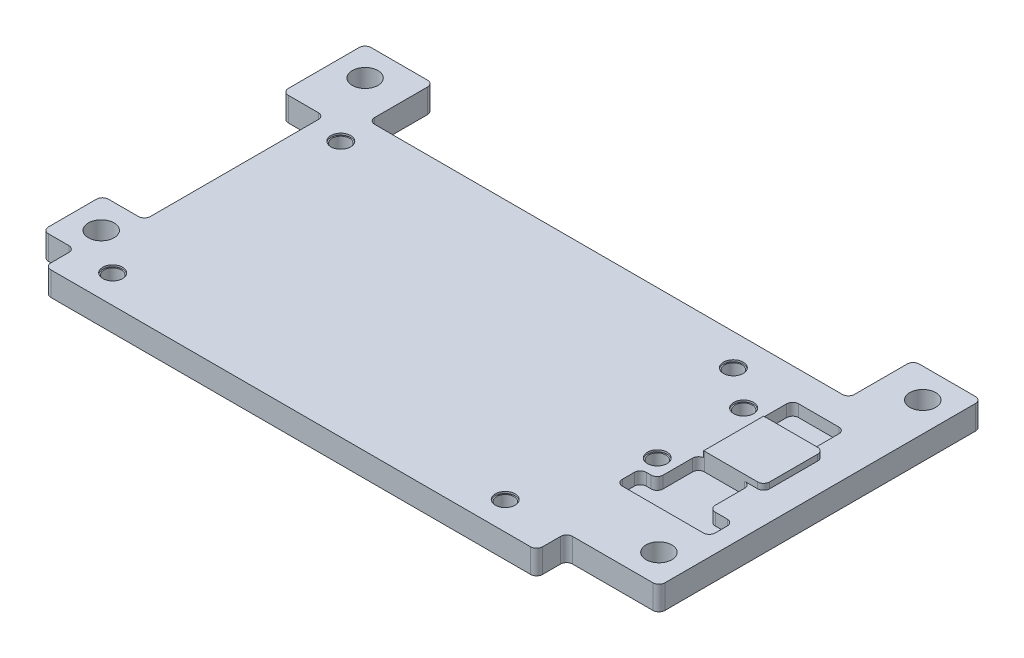
SolidWorks part; units mm, degrees
ref_plane "Front Plane" through (0, 0, 0) normal (0, 0, 1) x (1, 0, 0)
ref_plane "Top Plane" through (0, 0, 0) normal (0, 1, 0) x (1, 0, 0)
ref_plane "Right Plane" through (0, 0, 0) normal (1, 0, 0) x (0, 0, -1)
sketch "Sketch1" plane through (0, 0, 0) normal (0, 1, 0) x (1, 0, 0)
  line L0 (-97.9, 0) -> (-97.9, -53.8) construction
  line L1 (0, 0) -> (-102.8, 0)
  line L2 (0, 0) -> (0, -53.8)
  line L3 (0, -53.8) -> (-15.4, -53.8)
  line L4 (-102.8, 0) -> (-102.8, -53.8)
  line L5 (-102.8, -4.9) -> (0.8959, -4.9) construction
  line L6 (-102.8, -48.9) -> (0, -48.9) construction
  line L7 (-4.9, 0) -> (-4.9, -53.8) construction
  line L8 (-97.4, -53.8) -> (-97.4, -58.8)
  line L9 (-97.4, -58.8) -> (-15.4, -58.8)
  line L10 (-15.4, -58.8) -> (-15.4, -53.8)
  line L13 (-97.4, -53.8) -> (-102.8, -53.8)
  line L14 (-15.4, -53.8) -> (-97.4, -53.8) construction
  circle A0 centre (-97.9, -4.9) radius 2.15
  circle A1 centre (-97.9, -48.9) radius 2.15
  circle A2 centre (-4.9, -4.9) radius 2.15
  circle A3 centre (-4.9, -48.9) radius 2.15
  point P9 (-97.9, -4.9)
  point P14 (-4.9, -4.9)
  point P15 (-97.9, -48.9)
  point P16 (-4.9, -48.9)
  dimension "D7" = 4.3
  dimension "D1" = 102.8
  dimension "D2" = 53.8
  dimension "D3" = 4.9
  dimension "D4" = 4.9
  dimension "D5" = 4.9
  dimension "D6" = 4.9
  dimension "D8" = 82
  dimension "D9" = 5
  dimension "D10" = 5.4
extrude "Main" add sketch "Sketch1" along normal blind 4
sketch "Display Mount Locations" plane through (0, 4, 0) normal (0, 1, 0) x (1, 0, 0)
  line L1 (-90.8, -54.09) -> (-25.34, -54.09) construction
  line L2 (-90.8, -54.09) -> (-90.8, -16.05) construction
  line L3 (-90.8, -16.05) -> (-25.34, -16.05) construction
  line L4 (-25.34, -54.09) -> (-25.34, -16.05) construction
  line L5 (-90.8, -35.07) -> (-102.8, -35.07) construction
  line L7 (-102.8, 0) -> (-102.8, -53.8) construction
  line L9 (-15.4, -53.8) -> (0, -53.8) construction
  point P5 (-90.8, -16.05)
  point P6 (-25.34, -16.05)
  point P7 (-25.34, -54.09)
  point P8 (-90.8, -54.09)
  dimension "D1" = 65.46
  dimension "D2" = 38.04
  dimension "D3" = 0.29
  dimension "D4" = 12
sketch "Sketch4" plane through (0, 4, 0) normal (0, 1, 0) x (1, 0, 0)
  line L0 (-102.8, 0) -> (-102.8, -53.8) construction
  line L1 (-102.8, -13.8) -> (-95.8, -13.8)
  line L2 (-102.8, -13.8) -> (-102.8, -43.8)
  line L3 (-102.8, -43.8) -> (-95.8, -43.8)
  line L4 (-95.8, -13.8) -> (-95.8, -43.8)
  line L5 (-51.4, 0) -> (-51.4, -58.8) construction
  line L6 (0, 0) -> (-102.8, 0) construction
  line L8 (-102.8, -53.8) -> (-97.4, -53.8) construction
  line L13 (-97.4, -58.8) -> (-15.4, -58.8) construction
  dimension "D1" = 7
  dimension "D2" = 30
  dimension "D3" = 10
extrude "Wire Escapes" cut sketch "Sketch4" against normal up to next
sketch "Sketch5" plane through (0, 4, 0) normal (0, 1, 0) x (1, 0, 0)
  line L0 (0, 0) -> (-102.8, 0) construction
  line L1 (-91.4, 0) -> (-11.4, 0)
  line L2 (-91.4, 0) -> (-91.4, -10.8)
  line L3 (-91.4, -10.8) -> (-11.4, -10.8)
  line L4 (-11.4, 0) -> (-11.4, -10.8)
  line L5 (-91.4, -5.4) -> (-102.8, -5.4) construction
  line L7 (-11.4, -5.4) -> (0, -5.4) construction
  line L9 (-95.8, -13.8) -> (-102.8, -13.8) construction
  line L10 (-102.8, 0) -> (-102.8, -13.8) construction
  line L11 (0, -53.8) -> (0, 0) construction
  dimension "D1" = 80
  dimension "D2" = 3
extrude "Button Clearance" cut sketch "Sketch5" against normal up to next
sketch "Encoder Switch Mounting Points" plane through (0, 4, 0) normal (0, 1, 0) x (1, 0, 0)
  line L5 (0, -53.8) -> (0, 0) construction
  line L6 (-1, -15.8) -> (-19.7, -15.8) construction
  line L7 (-1, -15.8) -> (-1, -42.4) construction
  line L8 (-1, -42.4) -> (-19.7, -42.4) construction
  line L9 (-19.7, -15.8) -> (-19.7, -42.4) construction
  line L10 (-91.4, -10.8) -> (-11.4, -10.8) construction
  line L11 (-18.675, -15.8) -> (-18.675, -42.4) construction
  point P8 (-18.675, -35.4)
  point P9 (-18.675, -21)
  dimension "D1" = 1
  dimension "D2" = 18.7
  dimension "D3" = 26.6
  dimension "D4" = 5
  dimension "D5" = 2.05
  dimension "D6" = 5.2
  dimension "D7" = 7
hole_wizard "M2 Heat Sets" positions "3DSketch1" profile "Sketch3" counterbore size "M72" standard "ANSI Metric"
sketch3d "3DSketch1"
  point P0 (-90.8, 4, 16.05)
  point P3 (-90.8, 4, 54.09)
  point P6 (-25.34, 4, 54.09)
  point P9 (-25.34, 4, 16.05)
  point P12 (-18.675, 4, 21)
  point P15 (-18.675, 4, 35.4)
sketch "Sketch3" plane through (-90.8, 4, 16.05) normal (1, 0, 0) x (0, 0, 1)
  line L0 (0, 0) -> (0, 4)
  line L1 (0, 4) -> (1.45, 4)
  line L2 (1.45, 4) -> (1.45, 0.3)
  line L3 (1.45, 0.3) -> (1.65, 0.3)
  line L4 (1.65, 0.3) -> (1.65, 0)
  line L5 (1.65, 0) -> (0, 0)
  line L10 (0, 4) -> (-1.45, 4) construction
  line L11 (0, -6.35) -> (0, 107.95) construction
  dimension "Hole Dia." = 2.9
  dimension "Hole Depth" = 4
  dimension "C'Bore Dia." = 3.3
  dimension "C'Bore Depth" = 0.3
  dimension "Drill Angle" = 180
sketch "Sketch7" plane through (0, 4, 0) normal (0, 1, 0) x (1, 0, 0)
  line L0 (-14.8375, -26.5) -> (-18.675, -26.5) construction
  line L1 (-14.8375, -21.5) -> (-4.8375, -21.5)
  line L2 (-14.8375, -21.5) -> (-14.8375, -31.5)
  line L3 (-14.8375, -31.5) -> (-4.8375, -31.5)
  line L4 (-4.8375, -21.5) -> (-4.8375, -31.5)
  line L5 (-18.675, -15.8) -> (-18.675, -42.4) construction
  line L6 (-4.8375, -26.5) -> (-1, -26.5) construction
  line L7 (-1, -15.8) -> (-1, -42.4) construction
  dimension "D1" = 0.5
  dimension "D2" = 10
extrude "Encoder Standoff" add sketch "Sketch7" along normal blind 1
sketch "Sketch9" plane through (0, 4, 0) normal (0, 1, 0) x (1, 0, 0)
  line L0 (-1, -15.8) -> (-19.7, -15.8) construction
  line L1 (-15.7, -15.8) -> (-7, -15.8)
  line L5 (-1, -15.8) -> (-1, -42.4) construction
  line L7 (-19.7, -15.8) -> (-19.7, -42.4) construction
  line L9 (-15.7, -15.8) -> (-15.7, -21.5)
  line L10 (-15.7, -21.5) -> (-7, -21.5)
  line L11 (-7, -15.8) -> (-7, -21.5)
  line L13 (-4.8375, -21.5) -> (-14.8375, -21.5) construction
  line L16 (-14.8375, -31.5) -> (-4.8375, -31.5) construction
  line L17 (-15.7, -31.5) -> (-7, -31.5)
  line L18 (-15.7, -31.5) -> (-15.7, -38.4)
  line L20 (-7, -31.5) -> (-7, -38.4)
  line L21 (-1, -42.4) -> (-19.7, -42.4) construction
  line L22 (-15.7, -38.4) -> (-15.7, -42.4) construction
  line L23 (-18.5, -42.4) -> (-3, -42.4)
  line L24 (-18.5, -42.4) -> (-18.5, -38.4)
  line L25 (-18.5, -38.4) -> (-15.7, -38.4)
  line L26 (-3, -42.4) -> (-3, -38.4)
  line L27 (-7, -38.4) -> (-3, -38.4)
  line L28 (-15.7, -38.4) -> (-7, -38.4) construction
  line L29 (-7, -38.4) -> (-7, -42.4) construction
  point P14 (-7, -18.65)
  dimension "D1" = 4
  dimension "D2" = 15.5
  dimension "D3" = 4
  dimension "D4" = 6
  dimension "D5" = 4
extrude "Encoder Terminal Clearance" cut sketch "Sketch9" against normal blind 2
fillet "Fillet1" radius 1 30 edges at (0, 2, 0) (0, 2, 53.8) (-102.8, 2, 0) (-15.4, 2, 58.8) (-15.4, 2, 53.8) (-102.8, 2, 53.8) (-97.4, 2, 58.8) (-97.4, 2, 53.8) (-102.8, 2, 43.8) (-95.8, 2, 43.8) (-102.8, 2, 13.8) (-95.8, 2, 13.8) (-11.4, 2, 0) (-11.4, 2, 10.8) (-91.4, 2, 10.8) (-91.4, 2, 0) (-4.8375, 4.5, 21.5) (-4.8375, 4.5, 31.5) (-18.5, 3, 42.4) (-3, 3, 42.4) (-3, 3, 38.4) (-18.5, 3, 38.4) (-15.7, 3, 38.4) (-7, 3, 38.4) (-7, 3, 15.8) (-15.7, 3, 15.8) (-15.7, 3, 21.5) (-15.7, 3, 31.5) (-7, 3, 31.5) (-7, 3, 21.5)
